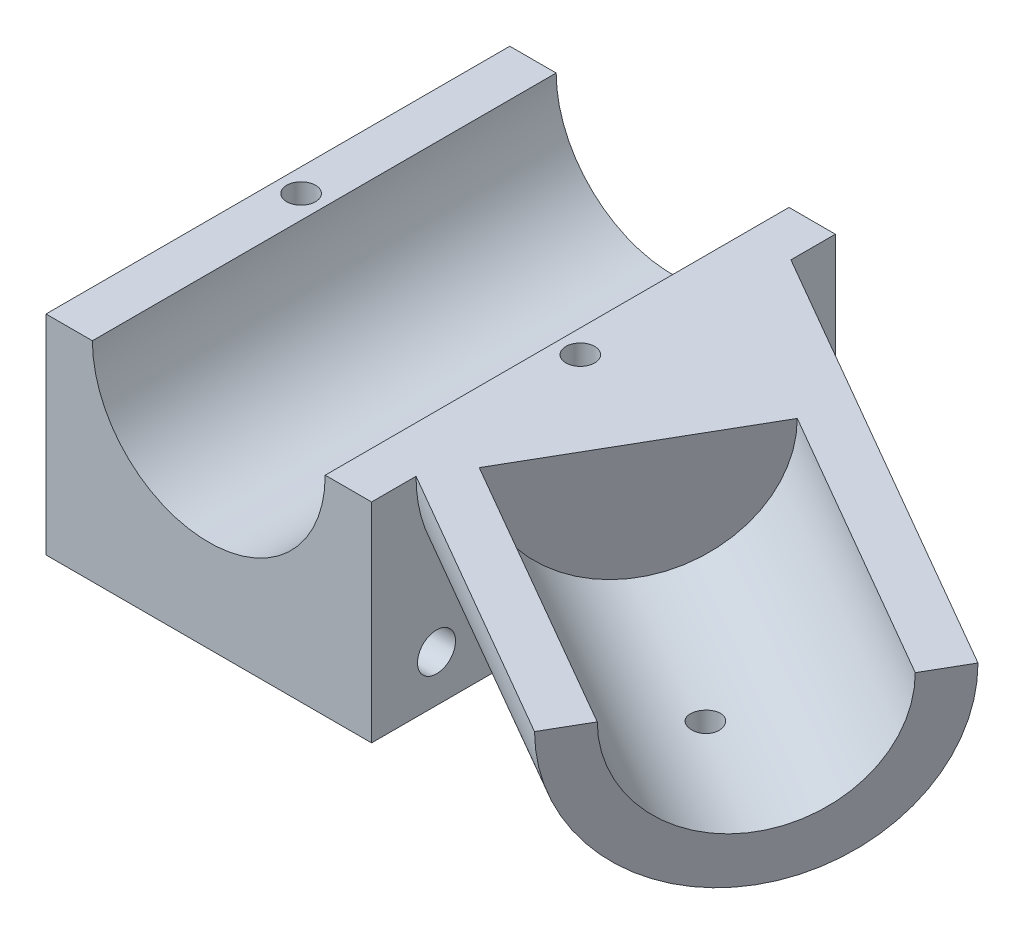
SolidWorks part; units mm, degrees
material "PLA"
ref_plane "Front Plane" through (0, 0, 0) normal (0, 0, 1) x (1, 0, 0)
ref_plane "Top Plane" through (0, 0, 0) normal (0, 1, 0) x (1, 0, 0)
ref_plane "Right Plane" through (0, 0, 0) normal (1, 0, 0) x (0, 0, -1)
sketch "Sketch1" plane through (0, 0, 0) normal (0, 0, 1) x (1, 0, 0)
  line L0 (-17.55, 22.5) -> (-17.55, 0)
  line L1 (55, 0) -> (-55, 0) construction
  line L2 (-17.55, 0) -> (17.55, 0)
  line L3 (17.55, 0) -> (17.55, 22.5)
  line L4 (-17.55, 22.5) -> (-12.55, 22.5)
  line L5 (17.55, 22.5) -> (12.55, 22.5)
  line L6 (0, -44.7868) -> (0, 44.7868) construction
  arc A0 (-12.55, 22.5) -> (12.55, 22.5) centre (0, 22.5) ccw
  dimension "D1" = 12.55
  dimension "D2" = 22.5
  dimension "D3" = 5
extrude "Boss-Extrude1" add sketch "Sketch1" along normal mid plane 50
sketch "Sketch2" plane through (0, 22.5, 0) normal (0, 1, 0) x (1, 0, 0)
  line L1 (-17.55, -25) -> (-17.55, 25) construction
  line L2 (12.55, -25) -> (12.55, 25) construction
  line L3 (-44.2539, 0) -> (44.2539, 0) construction
  circle A0 centre (-15.05, 0) radius 1.55
  circle A1 centre (15.05, 0) radius 1.55
  dimension "D1" = 3.1
  dimension "D4" = 2.5
  dimension "D5" = 2.5
extrude "Cut-Extrude1" cut sketch "Sketch2" against normal up to surface (22.5 mm away) up to face at (0, 0, 0)
sketch "Construct1" plane through (0, 0, 0) normal (0, 1, 0) x (1, 0, 0)
  line L0 (17.55, 0) -> (43.5308, -15) construction
  line L1 (-44.2539, 0) -> (44.2539, 0) construction
  line L2 (34.7676, -0.1782) -> (26.3131, -14.8218) construction
  line L3 (17.55, -25) -> (17.55, 25) construction
  point P6 (30.5404, -7.5)
  point P7 (30.5404, -7.5)
  dimension "D1" = 30
  dimension "D2" = 15
ref_plane "LegBuildPlane" through (26.1529, 0, 15.0994) normal (0.866, 0, 0.5) x (0.5, 0, -0.866)
sketch "Sketch5" plane through (26.1529, 0, 15.0994) normal (0.866, 0, 0.5) x (0.5, 0, -0.866)
  line L0 (-8.725, 22.5) -> (-3.775, 22.5)
  line L1 (21.325, 22.5) -> (26.275, 22.5)
  line L2 (17.2295, 0) -> (0.3205, 0) construction
  arc A0 (-3.775, 22.5) -> (21.325, 22.5) centre (8.775, 22.5) ccw
  arc A1 (-8.725, 22.5) -> (26.275, 22.5) centre (8.775, 22.5) ccw
  point P9 (8.775, 0)
  dimension "D1" = 17.5
  dimension "D2" = 12.55
  dimension "D3" = 22.5
  dimension "D4" = 0
extrude "Boss-Extrude2" add sketch "Sketch5" against normal up to surface and the other way blind 30 up to face at (17.55, 11.25, 0)
sketch "Sketch7" plane through (0, 22.5, 0) normal (0, 1, 0) x (1, 0, 0)
  line L0 (17.55, 0) -> (43.5308, -15) construction
  line L1 (50.2461, -33.3686) -> (62.7961, -11.6314) construction
  circle A0 centre (43.5308, -15) radius 1.55
  dimension "D1" = 3.1
  dimension "D2" = 15
extrude "Cut-Extrude2" cut sketch "Sketch7" against normal up to surface (17.4828 mm away) up to face at (37.0356, 13.75, 11.25)
sketch "Sketch9" plane through (-17.55, 0, 0) normal (-1, 0, 0) x (0, 0, 1)
  line L0 (25, 22.5) -> (25, 0) construction
  line L1 (0.1782, 0) -> (14.8218, 0) construction
  circle A0 centre (-18, 5) radius 2.05
  circle A1 centre (18, 5) radius 2.05
  dimension "D3" = 4.1
  dimension "D1" = 7
  dimension "D2" = 36
  dimension "D4" = 5
extrude "Cut-Extrude3" cut sketch "Sketch9" against normal up to surface (35.1 mm away) up to face at (17.55, 12.0833, 0)
sketch "Construct2" plane through (0, 22.5, 0) normal (0, 1, 0) x (1, 0, 0)
  line L0 (20.1481, -15.9915) -> (32.6981, 5.7457) construction
  line L2 (50.2461, -33.3686) -> (17.55, -14.4915) construction
  line L3 (62.7961, -11.6314) -> (17.55, 14.4915) construction
  line L4 (17.55, 0) -> (26.4231, -5.1229) construction
  line L11 (-44.2539, 0) -> (44.2539, 0) construction
  dimension "D1" = 3
  dimension "D2" = 90
ref_plane "LegBuildPlane2" through (22.0356, 0, 12.7222) normal (0.866, 0, 0.5) x (0.5, 0, -0.866)
sketch "Sketch12" plane through (22.0356, 0, 12.7222) normal (0.866, 0, 0.5) x (0.5, 0, -0.866)
  line L0 (-3.775, 22.5) -> (21.325, 22.5)
  arc A0 (-3.775, 22.5) -> (21.325, 22.5) centre (8.775, 22.5) ccw
extrude "Boss-Extrude5" add sketch "Sketch12" against normal up to surface (17.4915 mm away) up to face at (17.55, 16.225, 0)
equation "\"TubeDiam\"=12.55"
equation "\"D1@Sketch1\"=\"TubeDiam\""
equation "\"D2@Sketch1\"=\"ClampHeight\""
equation "\"MountLength\"=50"
equation "\"D1@Boss-Extrude1\"=\"MountLength\""
equation "\"MountHoleSize\"=3.1"
equation "\"D1@Sketch2\"=\"MountHoleSize\""
equation "\"LipWidth\"= 5"
equation "\"D3@Sketch1\"=\"LipWidth\""
equation "\"D4@Sketch2\"=\"LipWidth\"/2"
equation "\"D5@Sketch2\"=\"LipWidth\"/2"
equation "\"LegDiam\"=12.55"
equation "\"LegThickness\"= \"TubeDiam\" + 4.95"
equation "\"D1@Sketch5\"=\"LegThickness\""
equation "\"D2@Sketch5\"=\"TubeDiam\""
equation "\"ClampHeight\"= \"TubeDiam\" + 9.95"
equation "\"D3@Sketch5\"=\"ClampHeight\""
equation "\"D1@Sketch7\"=\"MountHoleSize\""
equation "\"HubHoleDist\"=7"
equation "\"D1@Sketch9\"=\"HubHoleDist\""
equation "\"D2@Sketch9\"=\"MountLength\"- 2 *\"HubHoleDist\""
equation "\"HubHoleSize\"=4.1"
equation "\"D3@Sketch9\"=\"HubHoleSize\""
